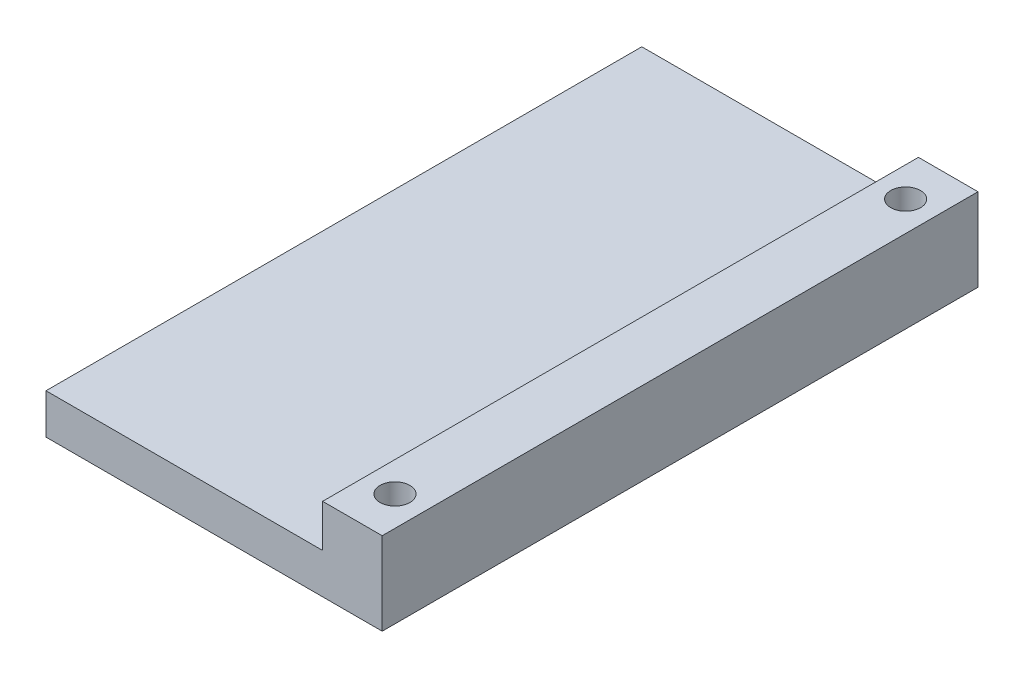
SolidWorks part; units mm, degrees
ref_plane "Front Plane" through (0, 0, 0) normal (0, 0, 1) x (1, 0, 0)
ref_plane "Top Plane" through (0, 0, 0) normal (0, 1, 0) x (1, 0, 0)
ref_plane "Right Plane" through (0, 0, 0) normal (1, 0, 0) x (0, 0, -1)
sketch "Sketch1" plane through (0, 0, 0) normal (0, 1, 0) x (1, 0, 0)
  line L1 (0, 0) -> (41.275, 0)
  line L2 (0, 0) -> (0, 88.9)
  line L3 (0, 88.9) -> (41.275, 88.9)
  line L4 (41.275, 0) -> (41.275, 88.9)
  line L5 (41.275, 88.9) -> (50.165, 88.9)
  line L6 (41.275, 88.9) -> (41.275, 0)
  line L7 (41.275, 0) -> (50.165, 0)
  line L8 (50.165, 88.9) -> (50.165, 0)
  dimension "D1" = 41.275
  dimension "D2" = 88.9
  dimension "D3" = 8.89
extrude "Boss-Extrude1" add sketch "Sketch1" along normal blind 5.9944 contours L1 L4 L3 L2 region at (20.6375, 0, -44.45)
extrude "Boss-Extrude2" add sketch "Sketch1<5>" along normal blind 12.3444 contours L8 L5 L4 L7 region at (45.72, 0, -44.45)
sketch "Sketch1<5>" plane through (0, 0, 0) normal (0, 1, 0) x (1, 0, 0) same geometry as "Sketch1"
sketch "Sketch3" plane through (0, 12.3444, 0) normal (0, 1, 0) x (1, 0, 0)
  line L0 (45.72, 82.55) -> (45.72, 6.35) construction
  line L1 (50.165, 88.9) -> (50.165, 0) construction
  line L2 (41.275, 88.9) -> (50.165, 88.9) construction
  line L3 (0, 0) -> (0, 88.9) construction
  circle A0 centre (45.72, 82.55) radius 2.2225
  circle A1 centre (45.72, 6.35) radius 2.2225
  point P4 (45.72, 44.45)
  point P5 (0, 0)
  point P6 (50.165, 44.45)
  point P7 (45.72, 88.9)
  point P10 (45.72, 77.9874)
  dimension "D1" = 4.445
  dimension "D2" = 4.445
  dimension "D3" = 76.2
  dimension "D4" = 45.72
extrude "Cut-Extrude1" cut sketch "Sketch3" against normal through all both contours A1 | A0
